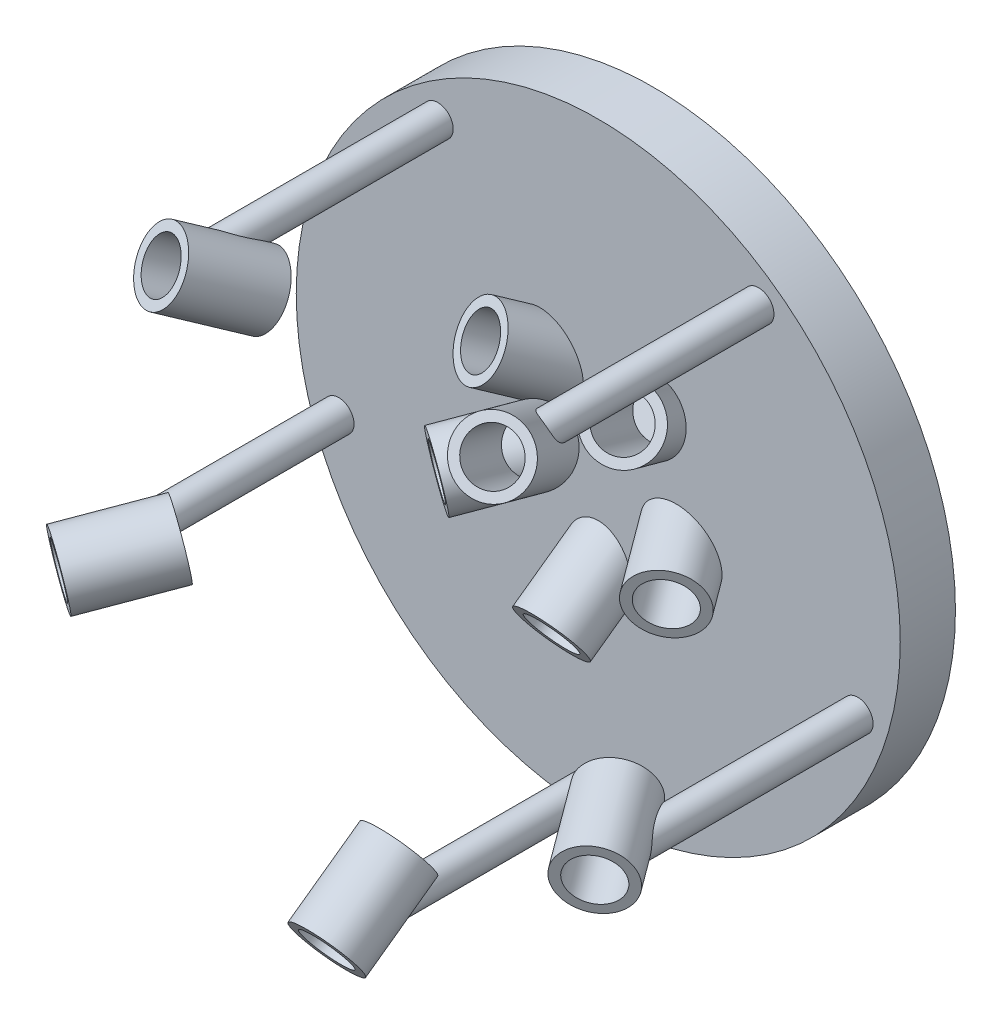
SolidWorks part; units mm, degrees
ref_plane "Front Plane" through (0, 0, 0) normal (0, 0, 1) x (1, 0, 0)
ref_plane "Top Plane" through (0, 0, 0) normal (0, 1, 0) x (1, 0, 0)
ref_plane "Right Plane" through (0, 0, 0) normal (1, 0, 0) x (0, 0, -1)
sketch "Sketch1" plane through (0, 0, 0) normal (0, 0, 1) x (1, 0, 0)
  circle A0 centre (0, 0) radius 98.5
  dimension "D1" = 197
extrude "Boss-Extrude1" add sketch "Sketch1" against normal mid plane 18 contours A0
sketch "Sketch2" plane through (0, 0, 0) normal (0, 0, 1) x (1, 0, 0)
  circle A0 centre (0, -22) radius 11
  dimension "D1" = 22
  dimension "D2" = 22
sketch "Sketch3" plane through (0, 0, 0) normal (1, 0, 0) x (0, 0, -1)
  line L0 (0, -22) -> (-97.537, -91.9037)
  line L1 (0, -11) -> (0, -33) construction
  dimension "D1" = 120
sweep "Sweep2" add path "Sketch3" circular profile diameter 22 parameters "D3"=22
sketch "Sketch65" plane through (0, 0, 0) normal (0, 0, 1) x (1, 0, 0)
  line L0 (0, -22) -> (0, -91.9037) construction
  circle A0 centre (0, -89) radius 5
  dimension "D1" = 89
extrude "Boss-Extrude2" add sketch "Sketch65" along normal blind 96
sweep "Cut-Sweep1" cut path "Sketch3<2>" circular profile diameter 16 parameters "D3"=16
sketch "Sketch3<2>" plane through (0, 0, 0) normal (1, 0, 0) x (0, 0, -1) same geometry as "Sketch3"
sketch "Sketch534" plane through (0, 0, 0) normal (1, 0, 0) x (0, 0, -1)
  line L0 (-24.2373, -39.3706) -> (-74.0164, -75.0467)
  line L1 (0, -22) -> (-97.537, -91.9037) construction
sweep "Cut-Sweep8" cut path "Sketch534" circular profile diameter 22 parameters "D3"=22
sketch "Sketch84" plane through (0, 0, 0) normal (1, 0, 0) x (0, 0, -1)
  line L0 (0, 0) -> (-200.8143, 0) construction
sketch "Sketch199" plane through (0, 0, 0) normal (1, 0, 0) x (0, 0, -1)
  line L0 (5.3176, -21.3084) -> (-9, -28.4502)
  line L1 (0, -22) -> (-97.537, -91.9037) construction
  line L2 (-9, -14.9169) -> (-9, -41.9835) construction
  dimension "D1" = 16
sweep "Cut-Sweep7" cut path "Sketch199" circular profile diameter 5 parameters "D3"=5
pattern_circular "CirPattern1" count 5 over 360 about axis through (0, 0, 0) along (0, 0, 1) of "Cut-Sweep1", "Boss-Extrude2", "Sweep2", "Cut-Sweep7", "Cut-Sweep8"
